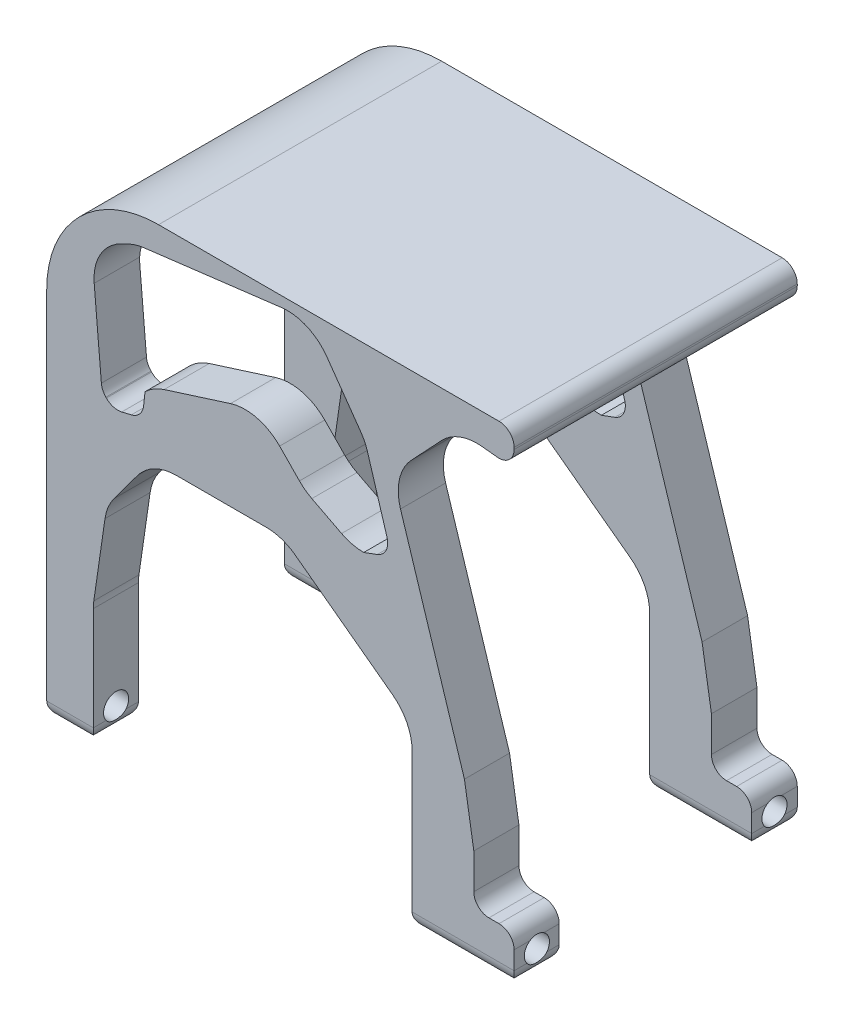
SolidWorks part; units mm, degrees
ref_plane "Front Plane" through (0, 0, 0) normal (0, 0, 1) x (1, 0, 0)
ref_plane "Top Plane" through (0, 0, 0) normal (0, 1, 0) x (1, 0, 0)
ref_plane "Right Plane" through (0, 0, 0) normal (1, 0, 0) x (0, 0, -1)
sketch "Sketch1" plane through (0, 0, 0) normal (0, 0, 1) x (1, 0, 0)
  line L1 (0, 0) -> (73.66, 0)
  line L2 (0, 0) -> (0, 76.2)
  line L3 (0, 76.2) -> (73.66, 76.2)
  line L4 (73.66, 0) -> (73.66, 76.2)
  dimension "D1" = 73.66
  dimension "D2" = 76.2
extrude "Boss-Extrude1" add sketch "Sketch1" along normal blind 44.6278
sketch "Sketch2" plane through (73.66, 0, 0) normal (1, 0, 0) x (0, 0, -1)
  line L0 (-44.6278, 0) -> (0, 0) construction
  line L1 (-37.5158, 0) -> (-7.1755, 0)
  line L2 (-37.5158, 0) -> (-37.5158, 62.23)
  line L3 (-29.8958, 69.85) -> (-14.7955, 69.85)
  line L4 (-7.1755, 0) -> (-7.1755, 62.23)
  line L5 (-44.6278, 0) -> (-44.6278, 76.2) construction
  arc A0 (-14.7955, 69.85) -> (-7.1755, 62.23) centre (-14.7955, 62.23) cw
  arc A1 (-37.5158, 62.23) -> (-29.8958, 69.85) centre (-29.8958, 62.23) cw
  point P12 (-7.1755, 69.85)
  dimension "D4" = 7.62
  dimension "D1" = 30.3403
  dimension "D2" = 69.85
  dimension "D3" = 7.112
extrude "Cut-Extrude1" cut sketch "Sketch2" against normal through all
sketch "Sketch3" plane through (0, 0, 44.6278) normal (0, 0, 1) x (1, 0, 0)
  line L0 (7.3406, 0) -> (7.3406, 41.4646) construction
  line L1 (0, 0) -> (73.66, 0) construction
  line L2 (57.5818, 0) -> (57.5818, 39.3354) construction
  line L3 (0, 76.2) -> (0, 0) construction
  line L4 (20.4271, 43.3819) -> (34.6128, 43.3819)
  line L5 (39.1531, 41.8815) -> (54.5022, 30.4935)
  line L6 (7.3406, 0) -> (7.3406, 18.6502)
  line L7 (7.4198, 19.7462) -> (9.1812, 31.864)
  line L8 (10.6023, 35.3083) -> (14.3075, 40.3022)
  line L9 (57.5818, 24.3739) -> (57.5818, 0)
  line L10 (57.5818, 0) -> (7.3406, 0)
  arc A0 (54.5022, 30.4935) -> (57.5818, 24.3739) centre (49.9618, 24.3739) cw
  arc A1 (34.6128, 43.3819) -> (39.1531, 41.8815) centre (34.6128, 35.7619) cw
  arc A2 (14.3075, 40.3022) -> (20.4271, 43.3819) centre (20.4271, 35.7619) cw
  arc A3 (9.1812, 31.864) -> (10.6023, 35.3083) centre (16.722, 30.7679) cw
  arc A4 (7.3406, 18.6502) -> (7.4198, 19.7462) centre (14.9606, 18.6502) cw
  point P15 (57.5818, 28.2086)
  point P24 (7.3406, 19.2011)
  dimension "D3" = 7.62
  dimension "D1" = 7.3406
  dimension "D2" = 50.2412
extrude "Cut-Extrude2" cut sketch "Sketch3" against normal blind 46.4439
fillet "Fillet4" radius 2.38 16 edges at (65.6209, 0, 7.1755) (57.5818, 0, 3.5877) (65.6209, 0, 0) (73.66, 0, 3.5878) (7.3406, 0, 3.5877) (3.6703, 0, 7.1755) (3.6703, 0, 0) (0, 0, 3.5877) (0, 0, 41.0718) (57.5818, 0, 41.0718) (3.6703, 0, 37.5158) (7.3406, 0, 41.0718) (3.6703, 0, 44.6278) (65.6209, 0, 37.5158) (73.66, 0, 41.0718) (65.6209, 0, 44.6278)
sketch "Sketch4" plane through (0, 0, 0) normal (-1, 0, 0) x (0, 0, 1)
  line L0 (-1.4585, 1.6002) -> (12.0714, 1.6002) construction
  line L1 (0, 76.2) -> (0, 2.38) construction
  circle A0 centre (3.5898, 3.5814) radius 1.9812
  point P4 (3.5898, 1.6002)
  dimension "D1" = 3.9624
  dimension "D2" = 1.6002
  dimension "D3" = 3.5898
extrude "Cut-Extrude3" cut sketch "Sketch4" against normal blind 110.4519
ref_plane "Plane1" through (0, 0, 22.3139) normal (0, 0, -1) x (-1, 0, 0)
mirror "Mirror1" about plane through (0, 0, 22.3139) normal (0, 0, -1) of "Cut-Extrude3"
sketch "Sketch5" plane through (0, 0, 0) normal (0, 0, -1) x (-1, 0, 0)
  line L0 (-73.66, 7.62) -> (-67.31, 7.62)
  line L1 (-73.66, 2.38) -> (-73.66, 76.2) construction
  line L2 (-67.31, 7.62) -> (-67.31, 15.567)
  line L3 (-67.31, 15.567) -> (-65.8315, 24.6228)
  line L4 (-65.8315, 24.6228) -> (-55.7534, 56.4569)
  line L5 (-57.4675, 63.9775) -> (-62.2441, 69.0559)
  line L6 (-68.5787, 71.4147) -> (-73.66, 70.889)
  line L7 (-73.66, 70.889) -> (-73.66, 7.62)
  line L8 (-15.2709, 71.8931) -> (-37.0088, 74.5755)
  line L9 (-44.1673, 71.4071) -> (-49.4813, 63.8788)
  line L12 (-28.962, 57.4496) -> (-18.5041, 54.1388)
  line L15 (-11.7606, 70.6477) -> (-12.8959, 71.1949)
  line L17 (-46.4676, 48.4733) -> (-41.7808, 50.8901)
  line L18 (-39.8321, 52.328) -> (-36.703, 55.5196)
  line L19 (-50.5206, 61.7844) -> (-53.6334, 51.5339)
  line L20 (-52.0862, 48.4144) -> (-49.96, 47.6258)
  line L21 (-7.4772, 63.1253) -> (-8.6094, 50.0634)
  line L22 (-9.3192, 48.5116) -> (-9.4002, 48.4283)
  line L24 (-15.4906, 52.328) -> (-15.4906, 52.3361)
  line L25 (-15.4906, 52.328) -> (-15.2648, 50.2854)
  line L26 (-13.3335, 48.0947) -> (-11.8142, 47.7297)
  line L27 (-59.9618, 0) -> (-71.28, 0) construction
  arc A0 (-49.96, 47.6258) -> (-46.4676, 48.4733) centre (-49.96, 55.2458) ccw
  arc A1 (-41.7808, 50.8901) -> (-39.8321, 52.328) centre (-45.2732, 57.6627) ccw
  arc A2 (-36.703, 55.5196) -> (-28.962, 57.4496) centre (-31.2619, 50.185) cw
  arc A3 (-18.5041, 54.1388) -> (-15.4906, 52.3361) centre (-20.804, 46.8742) cw
  arc A4 (-7.4772, 63.1253) -> (-11.7606, 70.6477) centre (-15.0688, 63.7833) ccw
  arc A5 (-15.2709, 71.8931) -> (-12.8959, 71.1949) centre (-16.2041, 64.3305) cw
  arc A6 (-37.0088, 74.5755) -> (-44.1673, 71.4071) centre (-37.942, 67.0129) ccw
  arc A7 (-49.4813, 63.8788) -> (-50.5206, 61.7844) centre (-43.256, 59.4846) ccw
  arc A8 (-55.7534, 56.4569) -> (-57.4675, 63.9775) centre (-63.018, 58.7568) ccw
  arc A9 (-62.2441, 69.0559) -> (-68.5787, 71.4147) centre (-67.7946, 63.8351) ccw
  arc A10 (-8.6094, 50.0634) -> (-9.3192, 48.5116) centre (-11.1399, 50.2827) cw
  arc A11 (-53.6334, 51.5339) -> (-52.0862, 48.4144) centre (-51.203, 50.7959) ccw
  arc A12 (-9.4002, 48.4283) -> (-11.8142, 47.7297) centre (-11.2209, 50.1995) cw
  arc A13 (-15.2648, 50.2854) -> (-13.3335, 48.0947) centre (-12.7402, 50.5645) ccw
  dimension "D1" = 7.62
  dimension "D2" = 2.54
  dimension "D3" = 2.54
  dimension "D4" = 6.35
  dimension "D5" = 7.62
extrude "Cut-Extrude4" cut sketch "Sketch5" against normal blind 110.4519
fillet "Fillet5" radius 17.62 1 edges at (0, 76.2, 22.3139)
fillet "Fillet6" radius 2.38 1 edges at (73.66, 70.889, 22.3139)
fillet "Fillet7" radius 2.38 4 edges at (73.66, 7.62, 41.0718) (67.31, 7.62, 41.0718) (73.66, 7.62, 3.5878) (67.31, 7.62, 3.5877)
fillet "Fillet8" radius 2.38 1 edges at (73.66, 76.2, 22.3139)
sketch "Sketch6" plane through (0, 76.2, 0) normal (0, 1, 0) x (1, 0, 0)
  line L0 (17.62, -22.3139) -> (71.28, -22.3139)
  line L1 (17.62, 0) -> (17.62, -44.6278) construction
  line L2 (71.28, -44.6278) -> (71.28, 0) construction
